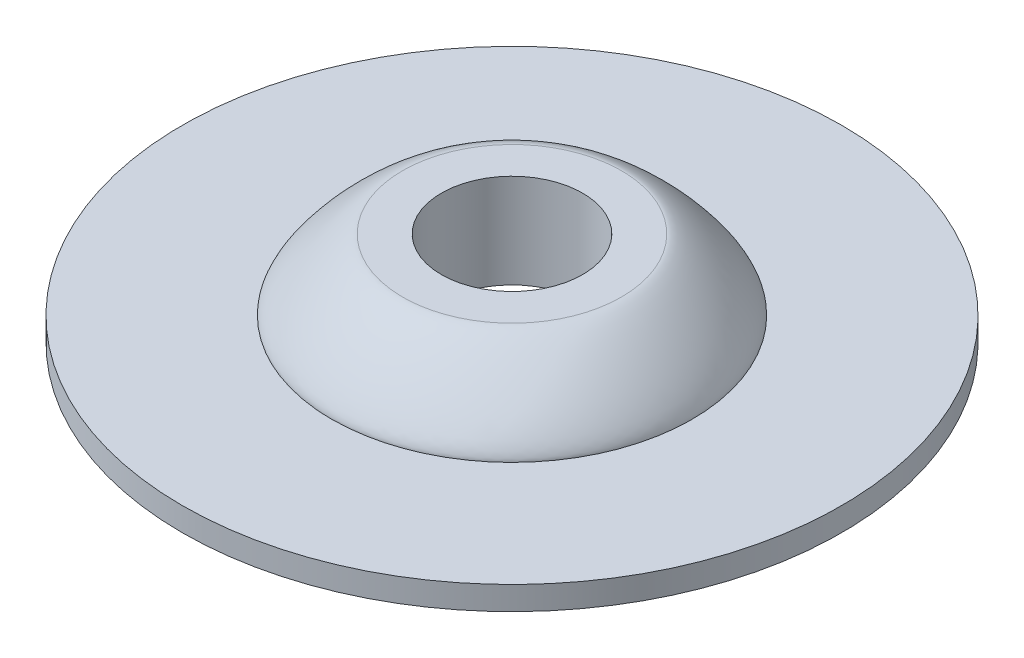
SolidWorks part; units mm, degrees
ref_plane "Plan de face" through (0, 0, 0) normal (0, 0, 1) x (1, 0, 0)
ref_plane "Plan de dessus" through (0, 0, 0) normal (0, 1, 0) x (1, 0, 0)
ref_plane "Plan de droite" through (0, 0, 0) normal (1, 0, 0) x (0, 0, -1)
sketch "Esquisse1" plane through (0, 0, 0) normal (0, 1, 0) x (1, 0, 0)
  circle A0 centre (0, 0) radius 14
  circle A1 centre (0, 0) radius 3
  dimension "D1" = 28
  dimension "D2" = 6
extrude "Boss.-Extru.1" add sketch "Esquisse1" along normal blind 1
sketch "Esquisse2" plane through (0, 1, 0) normal (0, 1, 0) x (1, 0, 0)
  circle A0 centre (0, 0) radius 7.65
  circle A1 centre (0, 0) radius 3
  dimension "D1" = 15.3
  dimension "D2" = 6
extrude "Boss.-Extru.2" add sketch "Esquisse2" along normal blind 3
fillet "Congé1" radius 3 1 edges at (0, 4, 7.65) conic radius 10
